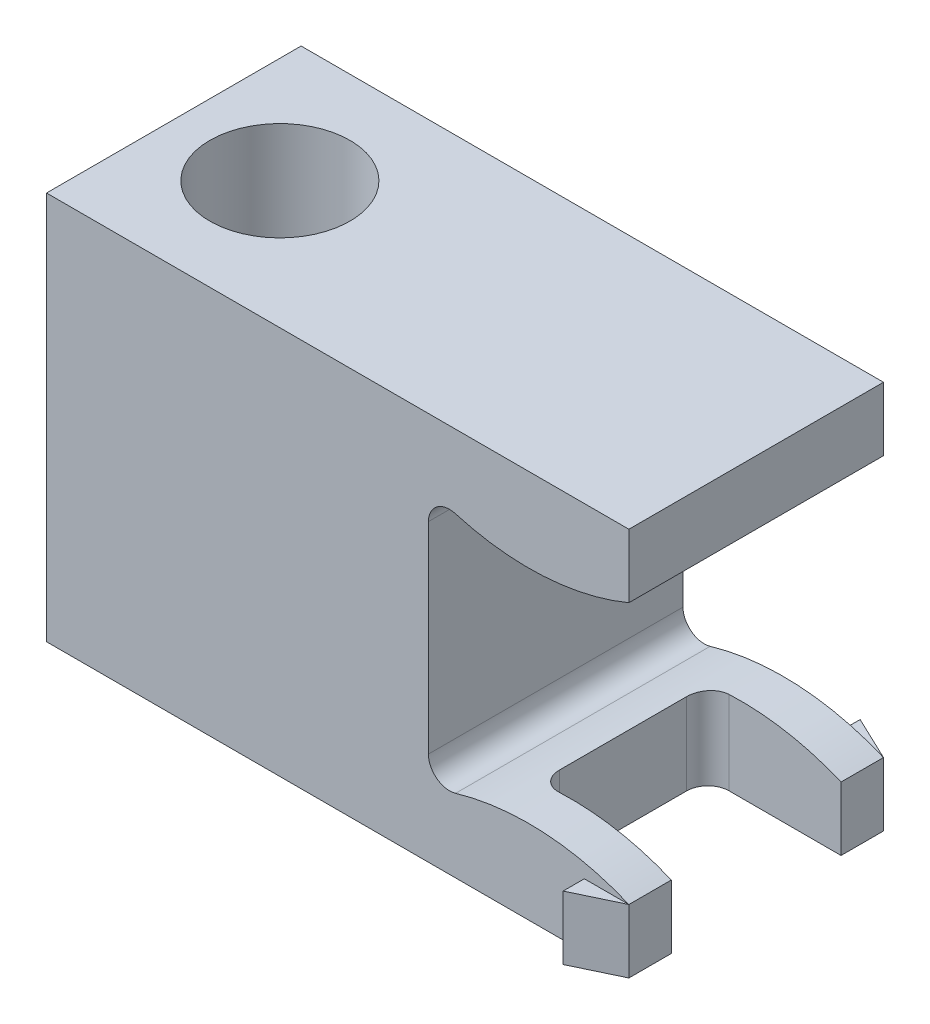
SolidWorks part; units mm, degrees
ref_plane "Front Plane" through (0, 0, 0) normal (0, 0, 1) x (1, 0, 0)
ref_plane "Top Plane" through (0, 0, 0) normal (0, 1, 0) x (1, 0, 0)
ref_plane "Right Plane" through (0, 0, 0) normal (1, 0, 0) x (0, 0, -1)
sketch "Sketch1" plane through (0, 0, 0) normal (0, 0, 1) x (1, 0, 0)
  line L2 (-159.7982, 9.1594) -> (-172.2482, 9.1594)
  line L3 (-172.2482, 9.1594) -> (-172.2482, -9.1594)
  line L7 (-169.2482, -22.8519) -> (-169.2482, 6.1594) construction
  line L12 (-169.2482, 5.1594) -> (-169.2482, 1.9844) construction
  line L13 (-142.8048, 5.1594) -> (-142.8048, -5.1594) construction
  line L15 (-156.5482, 5.1594) -> (21.2518, 5.1594) construction
  line L16 (-156.5482, -5.1594) -> (21.2518, -5.1594) construction
  line L23 (-159.7982, 6.1594) -> (-159.7982, 9.1594)
  line L28 (-164.5232, 5.2094) -> (-144.5007, 5.2094) construction
  line L29 (-156.5482, 5.1594) -> (-169.2482, 5.1594) construction
  line L30 (-169.2482, 6.1594) -> (-169.2482, 5.1594)
  line L34 (-169.2482, 5.1594) -> (-169.2482, -5.1594)
  line L35 (-172.2482, 0) -> (-169.2482, 0) construction
  line L36 (-169.2482, -6.1594) -> (-169.2482, -5.1594)
  line L37 (-159.7982, -6.1594) -> (-159.7982, -9.1594)
  line L38 (-159.7982, -9.1594) -> (-172.2482, -9.1594)
  line L39 (-159.7982, 5.1594) -> (-159.7982, 1.9844) construction
  arc A5 (-169.2482, 6.1594) -> (-159.7982, 6.1594) centre (-164.5232, 17.4347) ccw
  arc A6 (-169.2482, -6.1594) -> (-159.7982, -6.1594) centre (-164.5232, -17.4347) cw
  point P30 (-142.8048, 0)
  dimension "D4" = 3
  dimension "D3" = 3
  dimension "D2" = 1
extrude "MainBody" add sketch "Sketch1" along normal mid plane 12
sketch "Sketch3" plane through (0, -9.1594, 0) normal (0, -1, 0) x (1, 0, 0)
  line L0 (-159.7982, -6) -> (-161.8982, -7)
  line L1 (-161.8982, -7) -> (-161.8982, -6)
  line L2 (-172.2482, -6) -> (-159.7982, -6) construction
  line L3 (-161.8982, -6) -> (-159.7982, -6)
  line L4 (-162.8982, -12.7) -> (-162.8982, -6.35) construction
  line L5 (7.9475, 0) -> (-7.9475, 0) construction
  line L6 (-161.8982, 6) -> (-159.7982, 6)
  line L7 (-161.8982, 7) -> (-161.8982, 6)
  line L8 (-159.7982, 6) -> (-161.8982, 7)
  dimension "D1" = 1
  dimension "D2" = 1
extrude "Hook" add sketch "Sketch3" against normal up to vertex (3 mm away) up to point (-159.7982, -6.1594, -6)
sketch "Sketch4" plane through (0, -9.1594, 0) normal (0, -1, 0) x (1, 0, 0)
  line L0 (-159.7982, 6) -> (-159.7982, -6) construction
  line L1 (-159.7982, 4) -> (-166.0732, 4)
  line L2 (-159.7982, 4) -> (-159.7982, -4)
  line L3 (-159.7982, -4) -> (-166.0732, -4)
  line L4 (-166.0732, 4) -> (-166.0732, -4)
  line L5 (-172.2482, 6) -> (-172.2482, -6) construction
  line L6 (-172.2482, -6) -> (-161.8982, -6) construction
  line L7 (-162.8982, -6.35) -> (-169.2482, -6.35) construction
  point P6 (-166.0732, 0)
  point P9 (-172.2482, 0)
  point P14 (-166.0732, -6.35)
  dimension "D1" = 2
extrude "Flex" cut sketch "Sketch4" against normal up to next
fillet "Fillet1" radius 1 2 edges at (-166.0732, -7.2337, -4) (-166.0732, -7.2337, 4)
fillet "Fillet2" radius 1 2 edges at (-169.2482, 6.1594, 0) (-169.2482, -6.1594, 0)
sketch "Sketch5" plane through (-172.2482, 0, 0) normal (-1, 0, 0) x (0, 0, 1)
  line L1 (-6, 9.1594) -> (6, 9.1594)
  line L2 (-6, 9.1594) -> (-6, -9.1594)
  line L3 (-6, -9.1594) -> (6, -9.1594)
  line L4 (6, 9.1594) -> (6, -9.1594)
extrude "Boss-Extrude1" add sketch "Sketch5" along normal blind 15
sketch "Sketch6" plane through (0, 9.1594, 0) normal (0, 1, 0) x (1, 0, 0)
  line L0 (-187.2482, -6) -> (-187.2482, 6) construction
  circle A0 centre (-182.2482, 0) radius 3.302
  dimension "D1" = 6.604
  dimension "D2" = 5
extrude "Cut-Extrude2" cut sketch "Sketch6" against normal through all
equation "\"HookThickness\"= 3mm"
equation "\"D3@Sketch1\"=\"HookThickness\""
equation "\"D4@Sketch1\"=\"HookThickness\""
